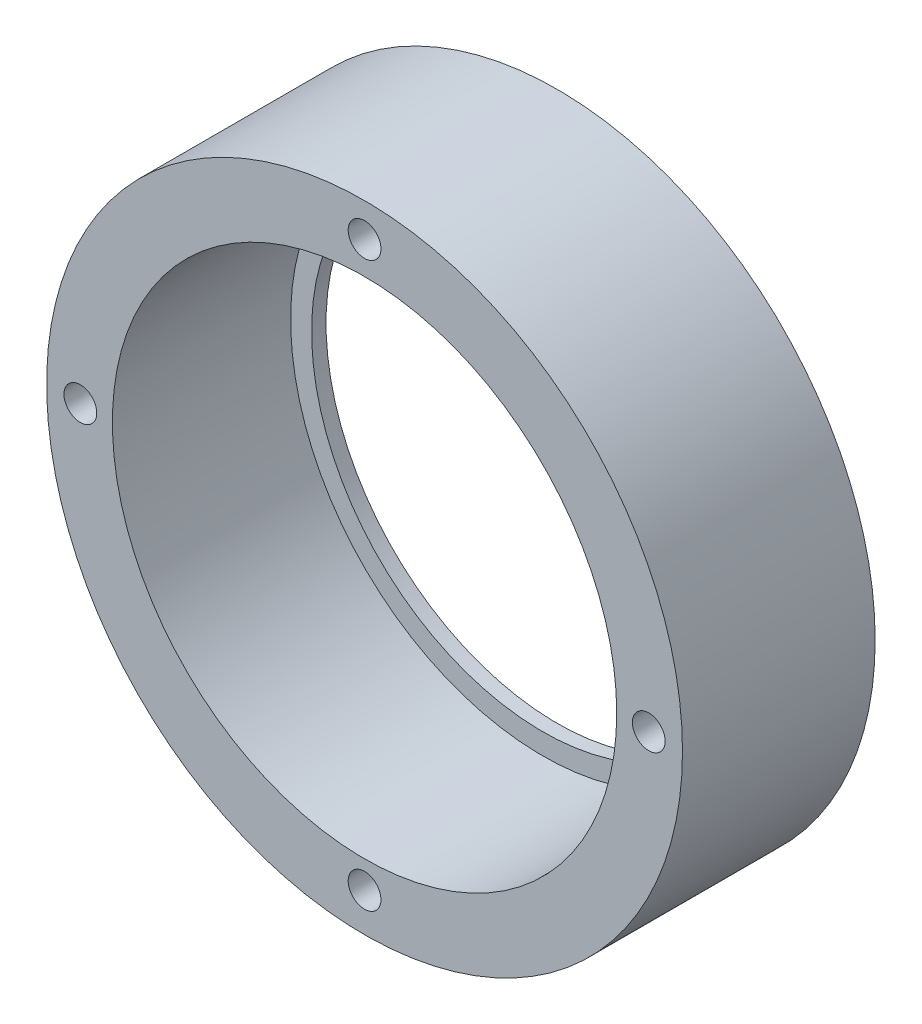
SolidWorks part; units mm, degrees
ref_plane "Front Plane" through (0, 0, 0) normal (0, 0, 1) x (1, 0, 0)
ref_plane "Top Plane" through (0, 0, 0) normal (0, 1, 0) x (1, 0, 0)
ref_plane "Right Plane" through (0, 0, 0) normal (1, 0, 0) x (0, 0, -1)
sketch "Sketch1" plane through (0, 0, 0) normal (0, 0, 1) x (1, 0, 0)
  circle A0 centre (0, 0) radius 33
  circle A1 centre (0, 0) radius 24
  dimension "D1" = 66
  dimension "D2" = 48
extrude "Boss-Extrude1" add sketch "Sketch1" along normal blind 1.5
sketch "Sketch3" plane through (0, 0, 1.5) normal (0, 0, 1) x (1, 0, 0)
  circle A0 centre (0, 0) radius 26.175
  circle A1 centre (0, 0) radius 33
  dimension "D1" = 52.35
  dimension "D2" = 66
extrude "Boss-Extrude2" add sketch "Sketch3" along normal blind 18.5
sketch "Sketch4" plane through (0, 0, 20) normal (0, 0, 1) x (1, 0, 0)
  circle A0 centre (0, 29.5) radius 1.7
  circle A1 centre (29.5, 0) radius 1.7
  circle A2 centre (0, -29) radius 1.7
  circle A3 centre (-29.5, 0) radius 1.7
  dimension "D1" = 3.4
  dimension "D2" = 3.4
  dimension "D3" = 3.4
  dimension "D4" = 3.4
  dimension "D5" = 29.5
  dimension "D6" = 29
  dimension "D7" = 29.5
  dimension "D8" = 29.5
extrude "Cut-Extrude1" cut sketch "Sketch4" against normal through all
chamfer "Chamfer1" distance 0.4 angle 45 4 edges at (1.7, -29, 0) (31.2, 0, 0) (-27.8, 0, 0) (1.7, 29.5, 0)
